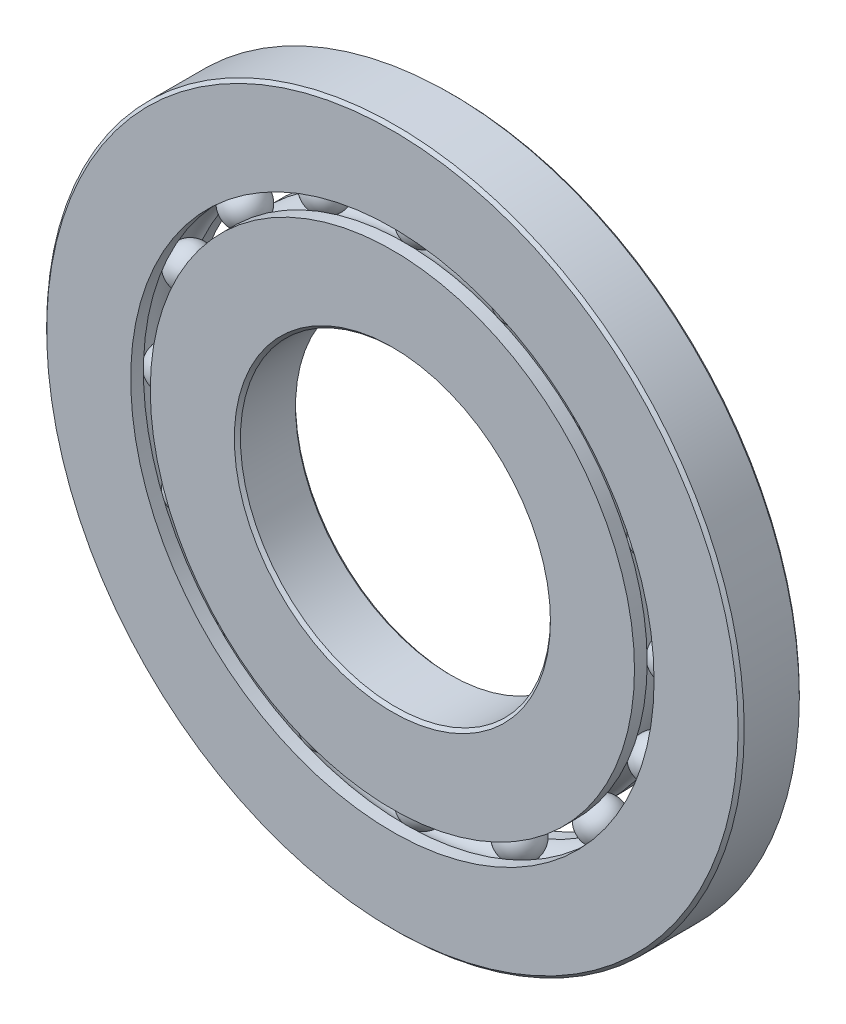
SolidWorks part; units mm, degrees
ref_plane "Front Plane" through (0, 0, 0) normal (0, 0, 1) x (1, 0, 0)
ref_plane "Top Plane" through (0, 0, 0) normal (0, 1, 0) x (1, 0, 0)
ref_plane "Right Plane" through (0, 0, 0) normal (1, 0, 0) x (0, 0, -1)
sketch "Sketch1" plane through (0, 0, 0) normal (1, 0, 0) x (0, 0, -1)
  line L0 (-0.395, 0) -> (0.395, 0) construction
  line L1 (0, 4.5) -> (0, -4.5) construction
  line L2 (0.3555, 4.5) -> (-0.3555, 4.5)
  line L3 (-0.3555, 4.5) -> (-0.395, 4.4605)
  line L4 (-0.395, 4.4605) -> (-0.395, 3.3763)
  line L5 (-0.395, 3.3763) -> (-0.2311, 3.3763)
  line L6 (0.395, 3.3763) -> (0.2311, 3.3763)
  line L7 (0.395, 4.4605) -> (0.395, 3.3763)
  line L8 (0.3555, 4.5) -> (0.395, 4.4605)
  line L9 (0, 4.5) -> (0, 3.25) construction
  line L10 (0, 3.25) -> (0, 2) construction
  circle A1 centre (0, 3.25) radius 0.2633 construction
  arc A2 (-0.2311, 3.3763) -> (0.2311, 3.3763) centre (0, 3.25) cw
  point P14 (0, 2)
  dimension "Ball Dia" = 0.5267
  dimension "Width" = 0.79
  dimension "OD" = 9
  dimension "D1" = 45
  dimension "D2" = 0.0395
  dimension "Shaft Dia" = 4
  dimension "D4" = 0.1263
revolve "Revolve1" add sketch "Sketch1" angle 360 about L0
sketch "Sketch3" plane through (0, 0, 0) normal (1, 0, 0) x (0, 0, -1)
  line L0 (-0.395, 3.1237) -> (-0.2311, 3.1237)
  line L1 (0, 4.5) -> (0, -4.5) construction
  line L2 (-0.395, 4.4605) -> (-0.395, 3.3763) construction
  line L3 (-0.395, 3.1237) -> (-0.395, 2.0395)
  line L4 (-0.3555, 4.5) -> (-0.395, 4.4605) construction
  line L5 (-0.395, 2.0395) -> (-0.3555, 2)
  line L6 (-0.3555, 2) -> (0.3555, 2)
  line L7 (0.3555, 4.5) -> (0.3555, -4.5) construction
  line L8 (0.3555, 2) -> (0.395, 2.0395)
  line L10 (0.395, 2.0395) -> (0.395, 3.1237)
  line L11 (0.395, 3.1237) -> (0.2311, 3.1237)
  line L13 (0.3555, 4.5) -> (0.395, 4.4605) construction
  arc A1 (0.2311, 3.1237) -> (-0.2311, 3.1237) centre (0, 3.25) cw
  circle A2 centre (0, 3.25) radius 0.2633 construction
revolve "Revolve3" add sketch "Sketch3" angle 360 about L0
sketch "Sketch4" plane through (0, 0, 0) normal (1, 0, 0) x (0, 0, -1)
  line L0 (-0.2633, 3.25) -> (0.2633, 3.25)
  circle A0 centre (0, 3.25) radius 0.2633 construction
  arc A2 (-0.2633, 3.25) -> (0.2633, 3.25) centre (0, 3.25) cw
revolve "Revolve4" add sketch "Sketch4" angle 360 about L0
ref_axis "Axis1" through (0, 0, -0.395) along (0, 0, 1)
pattern_circular "CirPattern1" count 16 every 22.5 about axis through (0, 0, -0.395) along (0, 0, 1) of bodies 104
equation "\"D2@Sketch1\" = \"Width@Sketch1\"*.05"
equation "\"D4@Sketch1\" = (((\"OD@Sketch1\"-\"Width@Sketch1\")/2)/3.25)*.1"
equation "\"D2@CirPattern1\" = 360/\"Balls@CirPattern1\""
